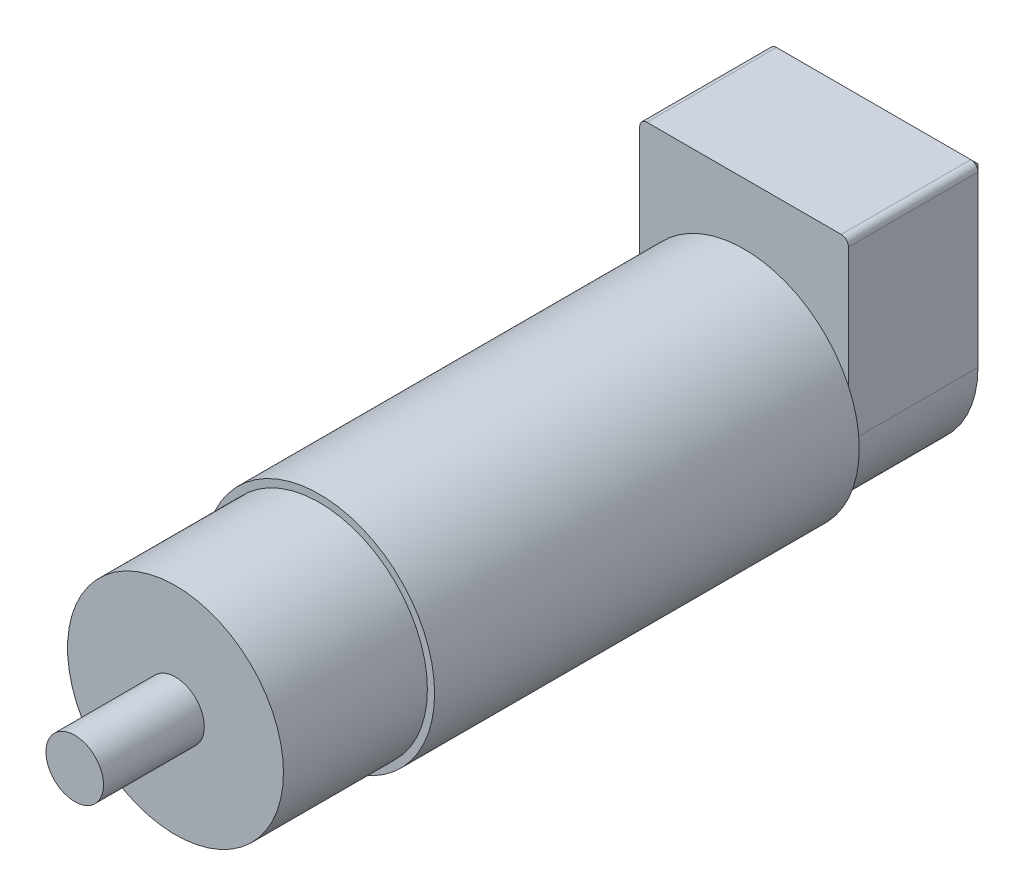
SolidWorks part; units mm, degrees
ref_plane "前基準面" through (0, 0, 0) normal (0, 0, 1) x (1, 0, 0)
ref_plane "上基準面" through (0, 0, 0) normal (0, 1, 0) x (1, 0, 0)
ref_plane "右基準面" through (0, 0, 0) normal (1, 0, 0) x (0, 0, -1)
sketch "草圖1" plane through (0, 0, 0) normal (0, 0, 1) x (1, 0, 0)
  circle A0 centre (0, 0) radius 16
  dimension "D1" = 32
extrude "填料-伸長1" add sketch "草圖1" along normal blind 79
sketch "草圖2" plane through (0, 0, 79) normal (0, 0, 1) x (1, 0, 0)
  circle A0 centre (0, 0) radius 4
  dimension "D1" = 8
extrude "填料-伸長2" add sketch "草圖2" along normal blind 14
sketch "草圖3" plane through (0, 0, 79) normal (0, 0, 1) x (1, 0, 0)
  circle A0 centre (0, 0) radius 16
  circle A1 centre (0, 0) radius 15
  circle A2 centre (0, 0) radius 16 construction
  dimension "D1" = 30
extrude "除料-伸長1" cut sketch "草圖3" against normal blind 20
sketch "草圖4" plane through (0, 0, 0) normal (0, 0, -1) x (-1, 0, 0)
  line L2 (14.5, 0) -> (14.5, 23.5)
  line L3 (13.5, 24.5) -> (-13.5, 24.5)
  line L4 (-14.5, 0) -> (-14.5, 23.5)
  arc A0 (-14.5, 0) -> (14.5, 0) centre (0, 0) ccw
  arc A1 (-13.5, 24.5) -> (-14.5, 23.5) centre (-13.5, 23.5) ccw
  arc A2 (14.5, 23.5) -> (13.5, 24.5) centre (13.5, 23.5) ccw
  point P2 (0, -14.5)
  dimension "D1" = 14.5
  dimension "D3" = 1
  dimension "D2" = 39
extrude "填料-伸長3" add sketch "草圖4" along normal blind 19
chamfer "導角1" distance 1 angle 45 6 edges at (0, 24.5, -19) (14.2071, 24.2071, -19) (-14.2071, 24.2071, -19) (14.5, 11.75, -19) (-14.5, 11.75, -19) (0, -14.5, -19)
